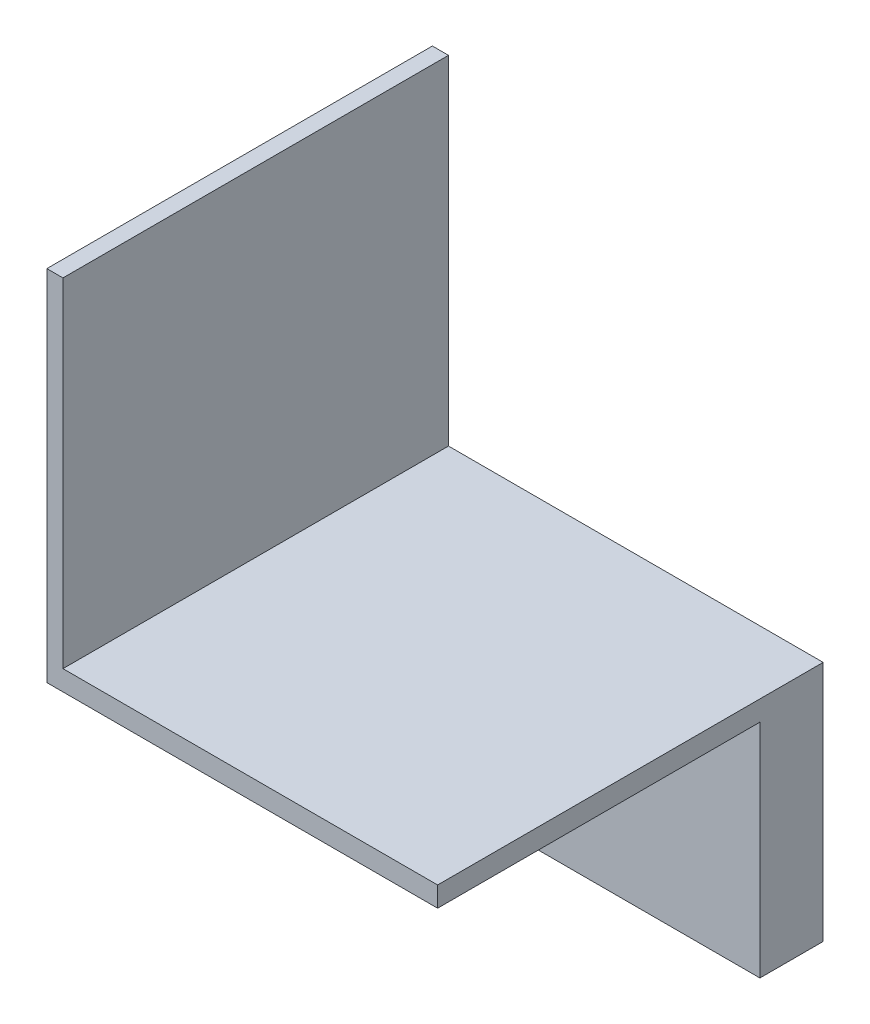
SolidWorks part; units mm, degrees
ref_plane "Front Plane" through (0, 0, 0) normal (0, 0, 1) x (1, 0, 0)
ref_plane "Top Plane" through (0, 0, 0) normal (0, 1, 0) x (1, 0, 0)
ref_plane "Right Plane" through (0, 0, 0) normal (1, 0, 0) x (0, 0, -1)
sketch "Sketch1" plane through (0, 0, 0) normal (0, 0, 1) x (1, 0, 0)
  line L1 (0, 0) -> (45.5, 0)
  line L2 (0, 0) -> (0, 27)
  line L3 (0, 27) -> (45.5, 27)
  line L4 (45.5, 0) -> (45.5, 27)
  dimension "D1" = 45.5
  dimension "D2" = 27
extrude "Boss-Extrude1" add sketch "Sketch1" along normal blind 7.85
sketch "Sketch3" plane through (0, 27, 0) normal (0, 1, 0) x (1, 0, 0)
  line L0 (45.5, 0) -> (0, 0) construction
  line L1 (45.5, 0) -> (-3, 0)
  line L2 (45.5, 0) -> (45.5, -7.85)
  line L3 (45.5, -7.85) -> (-3, -7.85)
  line L4 (-3, 0) -> (-3, -7.85)
  line L5 (45.5, -7.85) -> (45.5, 0) construction
  line L6 (45.5, -7.85) -> (0, -7.85) construction
  dimension "D1" = 48.5
extrude "Boss-Extrude2" add sketch "Sketch3" along normal blind 3
sketch "Sketch4" plane through (0, 0, 7.85) normal (0, 0, 1) x (1, 0, 0)
  line L0 (-3, 30) -> (45.5, 30) construction
  line L1 (45.5, 30) -> (-3, 30)
  line L2 (45.5, 30) -> (45.5, 27.5)
  line L3 (45.5, 27.5) -> (-3, 27.5)
  line L4 (-3, 30) -> (-3, 27.5)
  dimension "D1" = 2.5
  dimension "D2" = 48.5
extrude "Boss-Extrude3" add sketch "Sketch4" along normal blind 40
sketch "Sketch5" plane through (0, 30, 0) normal (0, 1, 0) x (1, 0, 0)
  line L0 (-3, 0) -> (-3, -47.85) construction
  line L1 (-3, 0) -> (-1, 0)
  line L2 (-3, 0) -> (-3, -47.85)
  line L3 (-3, -47.85) -> (-1, -47.85)
  line L4 (-1, 0) -> (-1, -47.85)
  line L5 (45.5, 0) -> (-3, 0) construction
  line L6 (45.5, -47.85) -> (-3, -47.85) construction
  dimension "D1" = 2
extrude "Boss-Extrude4" add sketch "Sketch5" along normal blind 42
